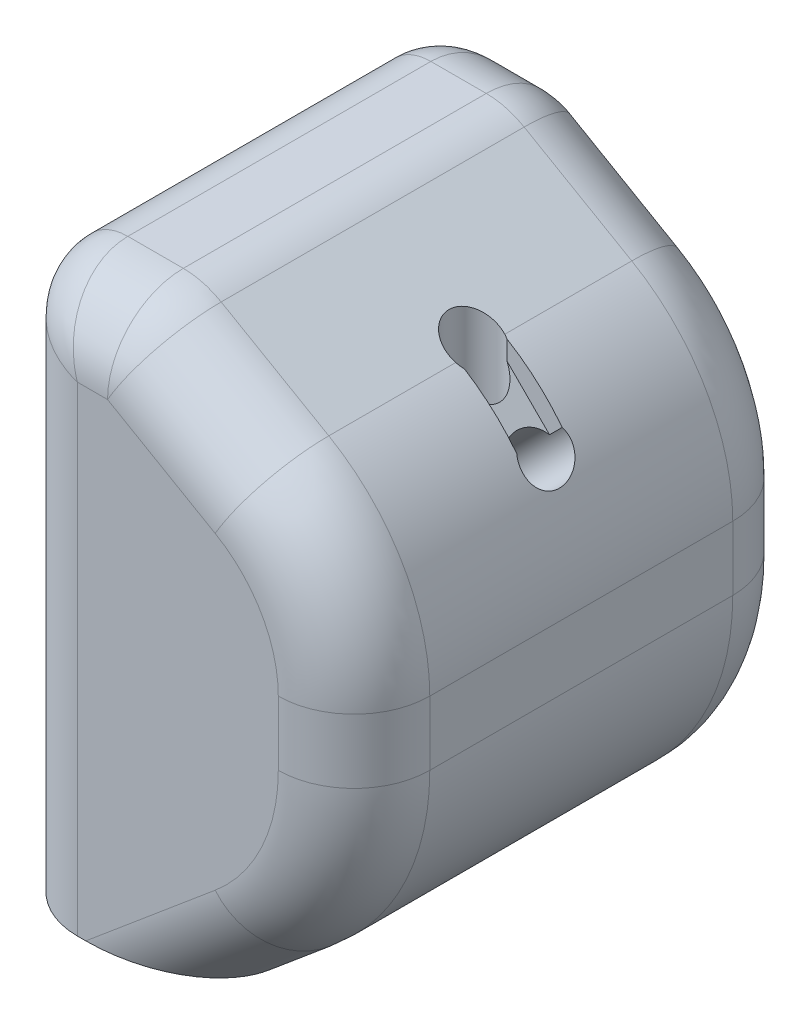
SolidWorks part; units mm, degrees
ref_plane "Front Plane" through (0, 0, 0) normal (0, 0, 1) x (1, 0, 0)
ref_plane "Top Plane" through (0, 0, 0) normal (0, 1, 0) x (1, 0, 0)
ref_plane "Right Plane" through (0, 0, 0) normal (1, 0, 0) x (0, 0, -1)
sketch "Sketch1" plane through (0, 0, 0) normal (0, 0, 1) x (1, 0, 0)
  line L0 (0, 0) -> (8, 0)
  line L1 (8, 0) -> (10.3866, 2.0026)
  line L2 (0, 0) -> (0, 20)
  line L3 (2, 22) -> (4.1962, 22)
  line L4 (5.6962, 21.5981) -> (9.9588, 19.1371)
  line L5 (13.9588, 12.2089) -> (13.9588, 9.6631)
  arc A0 (0, 20) -> (2, 22) centre (2, 20) cw
  arc A1 (5.6962, 21.5981) -> (4.1962, 22) centre (4.1962, 19) ccw
  arc A2 (13.9588, 12.2089) -> (9.9588, 19.1371) centre (5.9588, 12.2089) ccw
  arc A3 (13.9588, 9.6631) -> (10.3866, 2.0026) centre (3.9588, 9.6631) cw
  point P9 (0, 22)
  point P12 (5, 22)
  point P15 (13.9588, 16.8277)
  point P18 (13.9588, 5)
  dimension "D7" = 2
  dimension "D8" = 3
  dimension "D9" = 8
  dimension "D10" = 10
  dimension "D1" = 8
  dimension "D2" = 140
  dimension "D3" = 5
  dimension "D4" = 22
  dimension "D5" = 5
  dimension "D6" = 150
extrude "Boss-Extrude1" add sketch "Sketch1" along normal blind 18
sketch "Sketch2" plane through (0, 0, 0) normal (0, 0, -1) x (-1, 0, 0)
  line L0 (0, 0) -> (-8, 0) construction
  line L2 (-6, 0) -> (-4, 0)
  line L3 (-6, 0) -> (-6, 1.2087)
  line L5 (-4, 0) -> (-4, 1.2087)
  arc A0 (-4, 1.2087) -> (-6, 1.2087) centre (-5, 3.5) ccw
  point P0 (-5, 0)
  dimension "D2" = 5
  dimension "D1" = 5
  dimension "D3" = 3.5
  dimension "D4" = 2
  dimension "D5" = 1
extrude "Cut-Extrude1" cut sketch "Sketch2" against normal blind 13 from offset 2.5 offset against normal yes
sketch "Sketch4" plane through (0, 0, 0) normal (0, 1, 0) x (1, 0, 0)
  circle A0 centre (9.7202, -9) radius 1
  point P2 (0, 0)
  dimension "D1" = 2
  dimension "D2" = 9.7202
  dimension "D3" = 9
extrude "Cut-Extrude3" cut sketch "Sketch4" along normal blind 25
ref_plane "Plane1" through (14.5479, 14.5479, 0) normal (0.7071, 0.7071, 0) x (0, 0, -1)
sketch "Sketch5" plane through (14.5479, 14.5479, 0) normal (0.7071, 0.7071, 0) x (0, 0, -1)
  circle A0 centre (-8.9711, 2.99) radius 1
  point P0 (-8.9711, 6.49)
  dimension "D1" = 2
  dimension "D2" = 3.5
  dimension "D3" = 1
extrude "Cut-Extrude4" cut sketch "Sketch5" against normal blind 4 and the other way blind 2
fillet "Fillet1" radius 3 18 edges at (9.1933, 1.0013, 0) (13.0218, 5.4369, 0) (13.9588, 10.936, 0) (12.887, 16.2089, 0) (7.8275, 20.3676, 0) (4.9726, 21.8978, 0) (3.0981, 22, 0) (0.5858, 21.4142, 0) (9.1933, 1.0013, 18) (13.0218, 5.4369, 18) (13.9588, 10.936, 18) (12.887, 16.2089, 18) (7.8275, 20.3676, 18) (4.9726, 21.8978, 18) (3.0981, 22, 18) (0.5858, 21.4142, 18) (0, 10, 0) (0, 10, 18)
sketch "Sketch6" plane through (14.5479, 14.5479, 0) normal (0.7071, 0.7071, 0) x (0, 0, -1)
  line L1 (-9.8711, 2.99) -> (-8.0711, 2.99)
  line L2 (-9.8711, 2.99) -> (-9.8711, 6.7561)
  line L3 (-9.8711, 6.7561) -> (-8.0711, 6.7561)
  line L4 (-8.0711, 2.99) -> (-8.0711, 6.7561)
  circle A0 centre (-8.9711, 2.99) radius 1 construction
  ellipse E0 centre (-9, 6.7561) end of major axis (-9, 7.8714) minor radius 1 (-8.0289, 6.49) -> (-9.9711, 6.49) ccw construction
  ellipse E1 centre (-9, 6.7561) end of major axis (-9, 7.8714) minor radius 1 (-8.0289, 6.49) -> (-9.9711, 6.49) ccw construction
  point P5 (-9.5959, 3.7709)
  point P10 (-8.9711, 2.99)
  dimension "D1" = 1.8
  dimension "D2" = 0.9
  dimension "D3" = 0.1289
extrude "Cut-Extrude5" cut sketch "Sketch6" along normal blind 1 and the other way blind 0.5
sketch "Sketch7" plane through (0, 0, 0) normal (-1, 0, 0) x (0, 0, 1)
  line L0 (2.9999, 14.4276) -> (3, 10)
  line L1 (3, 20) -> (3, 0) construction
  line L2 (3, 10) -> (15, 10)
  line L3 (15, 0) -> (15, 20) construction
  line L4 (15, 10) -> (15, 14.4276)
  line L5 (15, 20) -> (3, 20) construction
  spline S0 degree 3 poles (2.9999, 14.4276) (2.3845, 21.2849) (9.084, 24.4107) (15.4091, 21.3672) (15, 14.4276) knots 0 0 0 0 0.49958 1 1 1 1
  dimension "D1" = 10
extrude "Cut-Extrude6" cut sketch "Sketch7" against normal blind 0.5
ref_plane "Plane2" through (0, 0, 9) normal (0, 0, 1) x (1, 0, 0)
